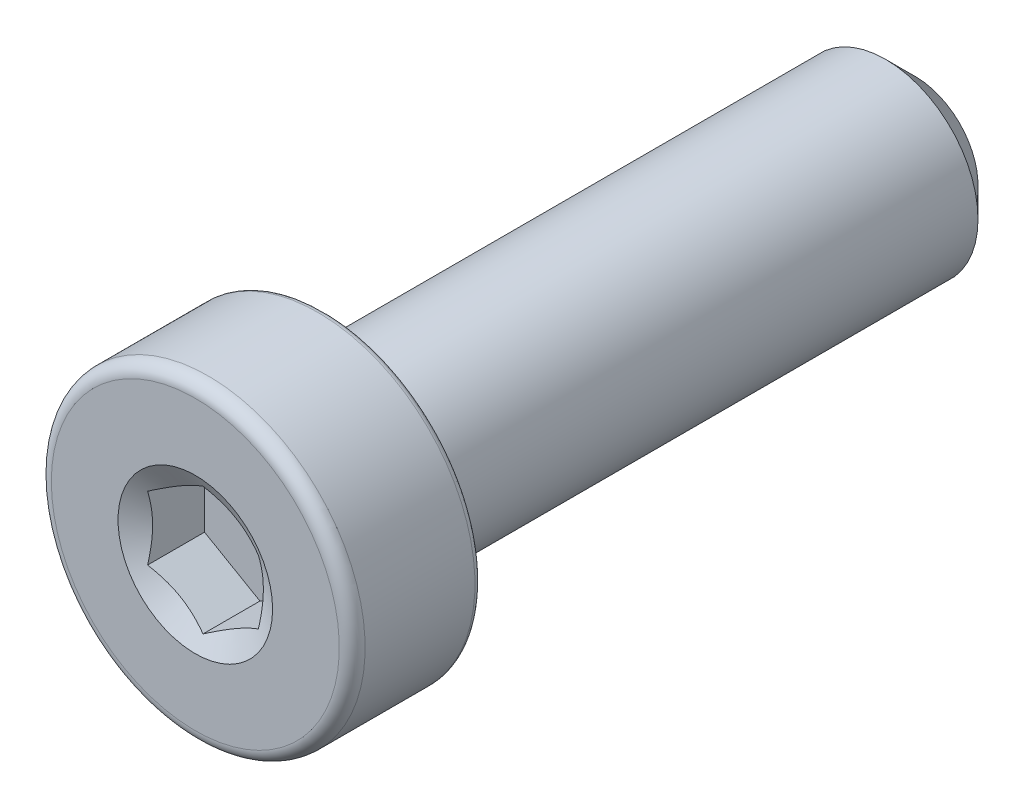
SolidWorks part; units mm, degrees
ref_plane "Front Plane" through (0, 0, 0) normal (0, 0, 1) x (1, 0, 0)
ref_plane "Top Plane" through (0, 0, 0) normal (0, 1, 0) x (1, 0, 0)
ref_plane "Right Plane" through (0, 0, 0) normal (1, 0, 0) x (0, 0, -1)
sketch "Sketch1" plane through (0, 0, 0) normal (1, 0, 0) x (0, 0, -1)
  line L0 (9.75, 0) -> (-9.75, 0) construction
  line L1 (-6.25, 4.25) -> (-6.25, -4.25) construction
  line L2 (9.75, 2.5) -> (9.75, -2.5) construction
  line L3 (9.7, 2.5866) -> (10.1, 1.8938) construction
  line L4 (10.05, 1.9804) -> (10.15, 1.9804) construction
  line L5 (10.1, 1.8938) -> (10.5, 2.5866) construction
  line L6 (10.5, 2.5866) -> (9.7, 2.5866) construction
  line L7 (10.1, 1.9804) -> (10.1, 1.8938) construction
  line L8 (10.1, 2.5866) -> (10.1, 2.5) construction
  line L9 (10.45, 2.5) -> (9.75, 2.5) construction
  line L10 (-9.75, -4.25) -> (-9.75, 4.25) construction
  point P4 (-6.25, 0)
  point P6 (-6.25, 1.5)
  point P7 (7.75, -2.5)
  point P20 (10.1, 2.5433)
  point P23 (-9.75, 0)
  point P24 (-6.25, 4.25)
  point P25 (-9.75, 4.25)
  point P26 (-9.75, -4.25)
  point P27 (-6.25, -4.25)
  point P28 (9.75, -2.5)
  point P29 (9.75, 2.5)
  dimension "Head Height" = 3.5
  dimension "Head Diameter" = 8.5
  dimension "Drive Size" = 3
  dimension "Length" = 16
  dimension "Thread Size" = 5
  dimension "Thread Pitch" = 0.8
  dimension "Pitch/8" = 0.1
  dimension "Thread Note" = 2
sketch "Sketch2" plane through (0, 0, 0) normal (1, 0, 0) x (0, 0, -1)
  line L0 (9.75, 0) -> (9.75, 1.7)
  line L1 (9.75, 2.5) -> (9.75, -2.5) construction
  line L2 (9.75, 1.7) -> (8.95, 2.5)
  line L3 (8.95, 2.5) -> (-6.25, 2.5)
  line L4 (-6.25, 2.5) -> (-6.25, 4.075)
  line L5 (-6.425, 4.25) -> (-9.4, 4.25)
  line L6 (-9.75, 3.9) -> (-9.75, 0)
  line L7 (9.75, 0) -> (-9.75, 0) construction
  line L8 (-9.75, 0) -> (9.75, 0)
  arc A0 (-6.25, 4.075) -> (-6.425, 4.25) centre (-6.425, 4.075) ccw
  arc A1 (-9.4, 4.25) -> (-9.75, 3.9) centre (-9.4, 3.9) ccw
  point P19 (-6.25, 4.25)
  dimension "D3" = 0.175
  dimension "D4" = 0.35
  dimension "D1" = 0.8
  dimension "D2" = 45
revolve "Revolve1" add sketch "Sketch2" angle 360 about L0
sketch "Sketch3" plane through (0, 0, 0) normal (0, 0, 1) x (1, 0, 0)
  line L0 (-1.5, -0.866) -> (1.5, -0.866) construction
  line L1 (-1.5, 0.866) -> (-1.5, -0.866)
  line L2 (-1.5, -0.866) -> (0, -1.7321)
  line L3 (0, -1.7321) -> (1.5, -0.866)
  line L4 (1.5, -0.866) -> (1.5, 0.866)
  line L5 (1.5, 0.866) -> (0, 1.7321)
  line L6 (0, 1.7321) -> (-1.5, 0.866)
  line L7 (-4.25, 0) -> (4.25, 0) construction
  circle A0 centre (0, 0) radius 1.5 construction
  circle A1 centre (0, 0) radius 4.25 construction
  point P12 (-1.5, -0.866)
  point P14 (1.5, -0.866)
  point P17 (-4.25, 0)
  point P18 (4.25, 0)
extrude "Cut-Extrude1" cut sketch "Sketch3" against normal blind 1.75 from vertex starting at point (0, 0, 9.75)
sketch "Sketch4" plane through (0, 0, 9.75) normal (0, 0, 1) x (1, 0, 0)
  line L0 (0, 1.7321) -> (0, 2.4547) construction
  line L1 (0, 2.4547) -> (0, 3.1774) construction
  line L2 (0, 3.1774) -> (0, 3.9) construction
  circle A0 centre (0, 0) radius 2.0934
  point P12 (0, 2.0934)
extrude "Cut-Extrude2" cut sketch "Sketch4" against normal through all draft 60
split "Split1" [suppressed] bodies to split 106 112
sketch "Sketch5" [suppressed] plane through (0, 0, 0) normal (1, 0, 0) x (0, 0, -1)
  line L0 (10.05, 1.9804) -> (10.15, 1.9804)
  line L1 (10.15, 1.9804) -> (10.475, 2.5433)
  line L2 (10.475, 2.5433) -> (9.725, 2.5433)
  line L3 (9.725, 2.5433) -> (10.05, 1.9804)
  line L4 (9.7, 2.5866) -> (10.1, 1.8938) construction
sketch "Sketch6" [suppressed] plane through (0, 0, -9.75) normal (0, 0, -1) x (-1, 0, 0)
  circle A0 centre (0, 0) radius 2.5
curve "Helix/Spiral1" [suppressed] pitch 0.8 height 16.8 turns 21
sweep "Cut-Sweep1" [suppressed] cut profiles "Sketch5" path "Helix/Spiral1"
sketch "Sketch7" [suppressed] plane through (0, 0, 6.25) normal (0, 0, -1) x (-1, 0, 0)
  circle A0 centre (0, 0) radius 2.5508
  circle A1 centre (0, 0) radius 2.5 construction
  dimension "D1" = 0.0508
extrude "Boss-Extrude1" [suppressed] add sketch "Sketch7" along normal blind 2.4 draft 20 and the other way blind 0.35
equation "\"Pitch/8@Sketch1\" = \"Thread Pitch@Sketch1\" / 8"
equation "\"Thread Note@Sketch1\" = \"Thread Pitch@Sketch1\" * 2.5"
equation "\"D1@Sketch2\" = \"Thread Pitch@Sketch1\""
equation "\"D3@Sketch2\"=\"Head Height@Sketch1\"*.05"
equation "\"D1@Cut-Extrude1\" = \"Head Height@Sketch1\" * .5"
equation "\"D3@Helix/Spiral1\" = \"Length@Sketch1\" + \"Thread Pitch@Sketch1\""
equation "\"D4@Helix/Spiral1\" = \"Thread Pitch@Sketch1\""
equation "\"D2@Boss-Extrude1\" = \"Head Height@Sketch1\" * .1"
equation "\"D1\"= \"Thread Size@Sketch1\" * .4"
equation "\"D1@Boss-Extrude1\" = \"Thread Pitch@Sketch1\" * 3"
equation "\"D4@Sketch2\"=\"D3@Sketch2\"*2"
